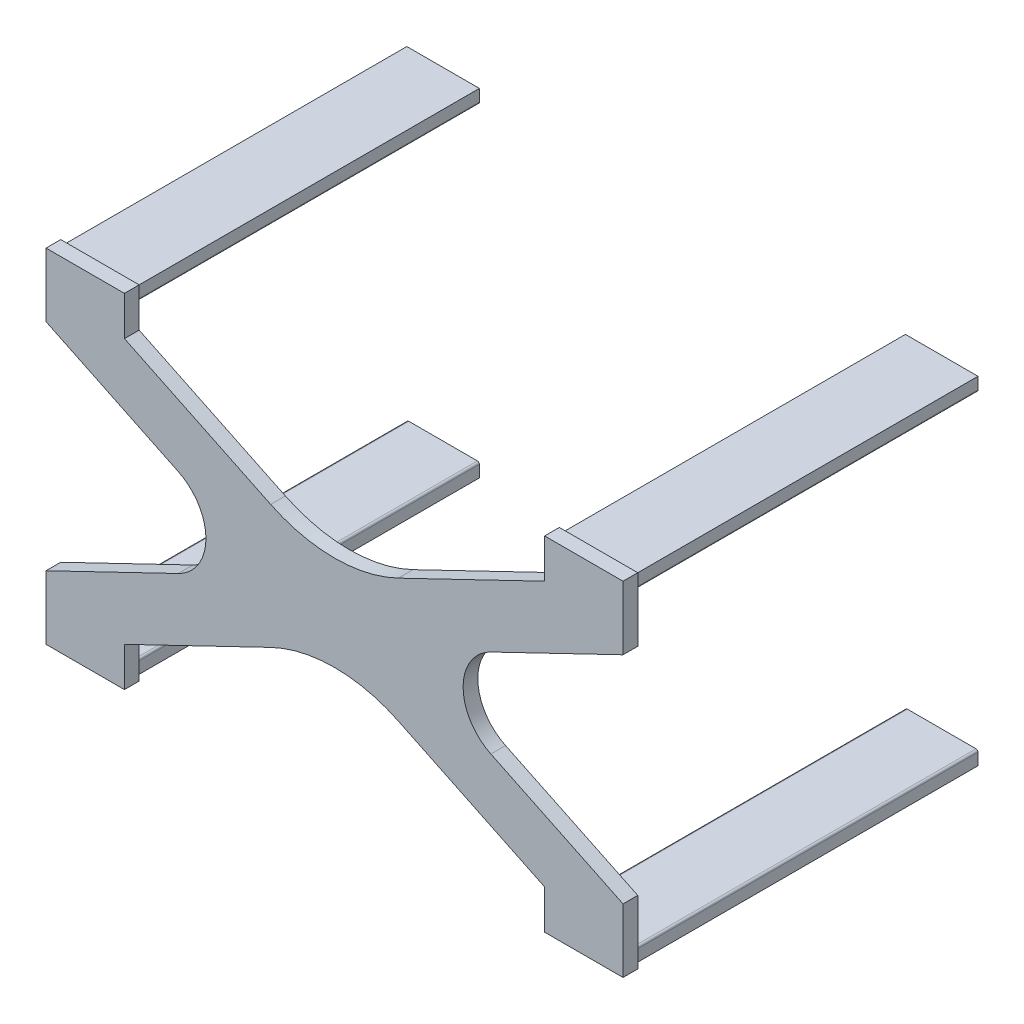
SolidWorks part; units mm, degrees
material "PETG"
ref_plane "Front Plane" through (0, 0, 0) normal (0, 0, 1) x (1, 0, 0)
ref_plane "Top Plane" through (0, 0, 0) normal (0, 1, 0) x (1, 0, 0)
ref_plane "Right Plane" through (0, 0, 0) normal (1, 0, 0) x (0, 0, -1)
sketch "Эскиз1" plane through (0, 0, 0) normal (0, 0, 1) x (1, 0, 0)
  line L0 (-50.85, 35) -> (-50.85, -35) construction
  line L1 (-85, -35) -> (85, -35)
  line L2 (-85, -35) -> (-85, 35)
  line L3 (-85, 35) -> (85, 35)
  line L4 (85, -35) -> (85, 35)
  line L5 (-85, -35) -> (85, 35) construction
  line L6 (-85, 35) -> (85, -35) construction
  line L7 (-85, 0) -> (85, 0) construction
  line L8 (-58.85, 35) -> (-58.85, 32)
  line L9 (-57.85, 31) -> (-43.85, 31)
  line L10 (-42.85, 32) -> (-42.85, 35)
  line L11 (0, 35) -> (0, -35) construction
  line L12 (-42.85, -32) -> (-42.85, -35)
  line L13 (-57.85, -31) -> (-43.85, -31)
  line L14 (-58.85, -35) -> (-58.85, -32)
  line L15 (58.85, -35) -> (58.85, -32)
  line L16 (57.85, -31) -> (43.85, -31)
  line L17 (42.85, -32) -> (42.85, -35)
  line L18 (42.85, 32) -> (42.85, 35)
  line L19 (57.85, 31) -> (43.85, 31)
  line L20 (58.85, 35) -> (58.85, 32)
  line L21 (-58.85, 32) -> (-58.85, 22)
  line L22 (-58.85, 22) -> (42.85, -27)
  line L23 (42.85, -27) -> (42.85, -32)
  line L24 (-42.85, 32) -> (-42.85, 27)
  line L25 (-42.85, 27) -> (58.85, -22)
  line L26 (58.85, -22) -> (58.85, -32)
  line L27 (42.85, 32) -> (42.85, 27)
  line L28 (42.85, 27) -> (-58.85, -22)
  line L29 (-58.85, -22) -> (-58.85, -32)
  line L30 (58.85, 32) -> (58.85, 22)
  line L31 (58.85, 22) -> (-42.85, -27)
  line L32 (-42.85, -27) -> (-42.85, -32)
  arc A0 (-43.85, 31) -> (-42.85, 32) centre (-43.85, 32) ccw
  arc A1 (-58.85, 32) -> (-57.85, 31) centre (-57.85, 32) ccw
  arc A2 (-43.85, -31) -> (-42.85, -32) centre (-43.85, -32) cw
  arc A3 (-58.85, -32) -> (-57.85, -31) centre (-57.85, -32) cw
  arc A4 (58.85, -32) -> (57.85, -31) centre (57.85, -32) ccw
  arc A5 (43.85, -31) -> (42.85, -32) centre (43.85, -32) ccw
  arc A6 (43.85, 31) -> (42.85, 32) centre (43.85, 32) cw
  arc A7 (58.85, 32) -> (57.85, 31) centre (57.85, 32) cw
  point P0 (0, 0)
  point P16 (-42.85, 31)
  point P19 (-58.85, 31)
  dimension "D7" = 1
  dimension "D1" = 170
  dimension "D2" = 70
  dimension "D3" = 34.15
  dimension "D4" = 16
  dimension "D5" = 8
  dimension "D6" = 4
  dimension "D8" = 10
  dimension "D9" = 5
extrude "Бобышка-Вытянуть1" add sketch "Эскиз1" along normal blind 3 contours A1 L21 L22 L28 L25 L24 A0 L9 | L30 A7 L19 A6 L27 L28 L25 L31 | L29 A3 L13 A2 L32 L31 L22 L28 | A5 L16 A4 L26 L25 L31 L22 L23 | L31 L25 L28 L22 | L8 A1 L9 A0 L10 L3 | A3 L14 L1 L12 A2 L13 | L16 A5 L17 L1 L15 A4 | A7 L20 L3 L18 A6 L19 region at (-50.85, -33.012, 0) region at (-32.4124, -15.969, 0) region at (-50.85, 33.012, 0) region at (50.85, -33.012, 0) region at (-32.4124, 15.969, 0) region at (32.4124, -15.969, 0) region at (0, 0, 0) region at (50.85, 33.012, 0) region at (32.4124, 15.969, 0)
fillet "Скругление1" radius 30 2 edges at (0, -6.3545, 1.5) (0, 6.3545, 1.5)
fillet "Скругление2" radius 10 2 edges at (13.1888, 0, 1.5) (-13.1888, 0, 1.5)
sketch "Эскиз2" plane through (0, 0, 0) normal (0, 0, -1) x (-1, 0, 0)
  line L0 (42.85, 32) -> (42.85, 35) construction
  line L4 (57.85, 31) -> (43.85, 31) construction
  line L5 (58.85, 35) -> (58.85, 32) construction
  line L6 (-58.85, -35) -> (-58.85, -32) construction
  line L7 (-57.85, -31) -> (-43.85, -31) construction
  line L8 (58.85, -35) -> (58.85, -32) construction
  line L12 (57.85, -31) -> (43.85, -31) construction
  line L13 (42.85, -32) -> (42.85, -35) construction
  line L20 (-58.85, 35) -> (-58.85, 32) construction
  line L21 (-57.85, 31) -> (-43.85, 31) construction
  line L22 (-42.85, 32) -> (-42.85, 35) construction
  line L23 (-42.85, -32) -> (-42.85, -35) construction
  line L24 (85, -35) -> (-85, -35) construction
  line L26 (85, 35) -> (-85, 35) construction
  line L28 (42.85, 32) -> (42.85, 35)
  line L29 (-58.25, 34.4) -> (-58.25, 32)
  line L30 (-57.85, 31.6) -> (-43.85, 31.6)
  line L31 (-43.45, 32) -> (-43.45, 34.4)
  line L32 (57.85, 31) -> (43.85, 31)
  line L33 (58.85, 35) -> (58.85, 32)
  line L34 (-58.85, -35) -> (-58.85, -32)
  line L35 (-57.85, -31) -> (-43.85, -31)
  line L36 (58.85, -35) -> (58.85, -32)
  line L37 (-43.45, 34.4) -> (-58.25, 34.4)
  line L38 (-57.85, -31.6) -> (-43.85, -31.6)
  line L39 (-43.45, -32) -> (-43.45, -34.4)
  line L40 (57.85, -31) -> (43.85, -31)
  line L41 (42.85, -32) -> (42.85, -35)
  line L42 (-43.45, -34.4) -> (-58.25, -34.4)
  line L43 (-58.25, -34.4) -> (-58.25, -32)
  line L44 (58.25, -34.4) -> (58.25, -32)
  line L45 (57.85, -31.6) -> (43.85, -31.6)
  line L46 (43.45, -32) -> (43.45, -34.4)
  line L47 (58.25, -34.4) -> (43.45, -34.4)
  line L48 (-58.85, 35) -> (-58.85, 32)
  line L49 (-57.85, 31) -> (-43.85, 31)
  line L50 (-42.85, 32) -> (-42.85, 35)
  line L51 (-42.85, -32) -> (-42.85, -35)
  line L52 (58.85, -35) -> (42.85, -35)
  line L54 (58.85, 35) -> (42.85, 35)
  line L56 (-42.85, -35) -> (-58.85, -35)
  line L57 (-42.85, 35) -> (-58.85, 35)
  line L58 (43.45, 32) -> (43.45, 34.4)
  line L59 (58.25, 34.4) -> (43.45, 34.4)
  line L60 (58.25, 34.4) -> (58.25, 32)
  line L61 (57.85, 31.6) -> (43.85, 31.6)
  line L62 (-50.85, 34.4) -> (-50.85, 31.6) construction
  arc A0 (42.85, 32) -> (43.85, 31) centre (43.85, 32) ccw construction
  arc A1 (57.85, 31) -> (58.85, 32) centre (57.85, 32) ccw construction
  arc A2 (-42.85, -32) -> (-43.85, -31) centre (-43.85, -32) ccw construction
  arc A3 (-57.85, -31) -> (-58.85, -32) centre (-57.85, -32) ccw construction
  arc A4 (43.85, -31) -> (42.85, -32) centre (43.85, -32) ccw construction
  arc A5 (58.85, -32) -> (57.85, -31) centre (57.85, -32) ccw construction
  arc A6 (-43.85, 31) -> (-42.85, 32) centre (-43.85, 32) ccw construction
  arc A7 (-58.85, 32) -> (-57.85, 31) centre (-57.85, 32) ccw construction
  arc A8 (42.85, 32) -> (43.85, 31) centre (43.85, 32) ccw
  arc A9 (57.85, 31) -> (58.85, 32) centre (57.85, 32) ccw
  arc A10 (-42.85, -32) -> (-43.85, -31) centre (-43.85, -32) ccw
  arc A11 (-57.85, -31) -> (-58.85, -32) centre (-57.85, -32) ccw
  arc A12 (43.85, -31) -> (42.85, -32) centre (43.85, -32) ccw
  arc A13 (58.85, -32) -> (57.85, -31) centre (57.85, -32) ccw
  arc A14 (-43.85, 31) -> (-42.85, 32) centre (-43.85, 32) ccw
  arc A15 (-58.85, 32) -> (-57.85, 31) centre (-57.85, 32) ccw
  arc A16 (-58.25, 32) -> (-57.85, 31.6) centre (-57.85, 32) ccw
  arc A17 (-43.85, 31.6) -> (-43.45, 32) centre (-43.85, 32) ccw
  arc A18 (-43.45, -32) -> (-43.85, -31.6) centre (-43.85, -32) ccw
  arc A19 (-57.85, -31.6) -> (-58.25, -32) centre (-57.85, -32) ccw
  arc A20 (58.25, -32) -> (57.85, -31.6) centre (57.85, -32) ccw
  arc A21 (43.85, -31.6) -> (43.45, -32) centre (43.85, -32) ccw
  arc A22 (57.85, 31.6) -> (58.25, 32) centre (57.85, 32) ccw
  arc A23 (43.45, 32) -> (43.85, 31.6) centre (43.85, 32) ccw
  dimension "D1" = 0.6
  dimension "D2" = 0.6
  dimension "D3" = 0.6
  dimension "D4" = 0.6
extrude "Бобышка-Вытянуть2" add sketch "Эскиз2" along normal blind 70 separate body contours L62 L37 L29 A16 L30 | L37 L62 L30 A17 L31 | L38 A19 L43 L42 L39 A18 | L45 A21 L46 L47 L44 A20 | L58 A23 L61 A22 L60 L59 region at (54.544, 33.0022, 0) region at (47.156, 33.0022, 0) region at (50.85, -33.0022, 0) region at (-50.85, -33.0022, 0) region at (-50.85, 33.0022, 0)
